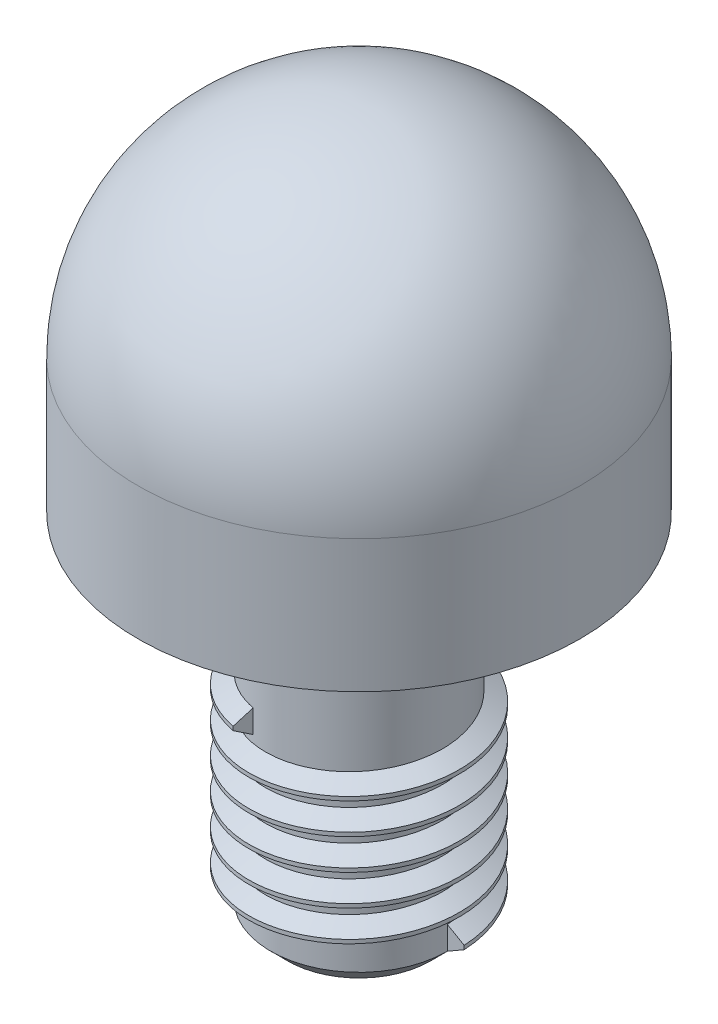
SolidWorks part; units mm, degrees
ref_plane "Piano frontale" through (0, 0, 0) normal (0, 0, 1) x (1, 0, 0)
ref_plane "Piano superiore" through (0, 0, 0) normal (0, 1, 0) x (1, 0, 0)
ref_plane "Piano destro" through (0, 0, 0) normal (1, 0, 0) x (0, 0, -1)
sketch "Schizzo1" plane through (0, 0, 0) normal (0, 0, 1) x (1, 0, 0)
  line L1 (0, 0) -> (5, 0)
  line L2 (0, 0) -> (0, 8)
  line L3 (0, 8) -> (5, 8)
  line L4 (5, 0) -> (5, 8)
  dimension "D1" = 5
  dimension "D2" = 8
revolve "Rivoluzione1" add sketch "Schizzo1" angle 360 about L2
sketch "Schizzo2" plane through (0, 0, 0) normal (0, -1, 0) x (1, 0, 0)
  circle A0 centre (0, 0) radius 2
  dimension "D1" = 4
extrude "Estrusione-Estrusione1" add sketch "Schizzo2" along normal blind 8
chamfer "Smusso2" distance 0.38 angle 45 1 edges at (2, -8, 0)
thread "Filettatura1" pitch 0.7 method extrude profile "Profilo filettatura2" start angle 0, offset 0, length 4, pitch 0.7, diameter 4
ref_plane "Piano2" through (2, -7.62, 0) normal (0, 0, 1) x (1, 0, 0)
sketch "Profilo filettatura2" plane through (2, -7.62, 0) normal (0, 0, 1) x (1, 0, 0)
  line L0 (0, 0) -> (0, 0.7) construction
  line L1 (0, 0) -> (0.3789, 0.2187)
  line L2 (0.3789, 0.2187) -> (0.3789, 0.3062)
  line L3 (0.3789, 0.3062) -> (0, 0.525)
  line L4 (0.3789, 0.2625) -> (0, 0.2625) construction
  line L11 (0, 0) -> (0, 0.525)
  point P2 (0, 0)
  dimension "Pitch" = 0.7
  dimension "Profile_Angle" = 60
  dimension "Profile_Land" = 0.0875
  dimension "Profile_Height" = 0.3789
fillet "Raccordo1" radius 5 1 edges at (5, 8, 0)
